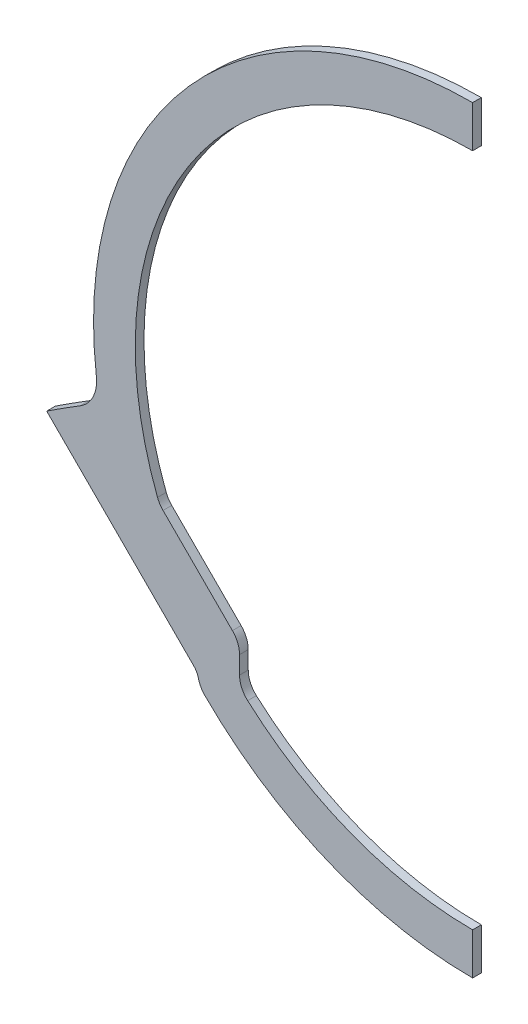
SolidWorks part; units mm, degrees
material "Balsa"
ref_plane "Front Plane" through (0, 0, 0) normal (0, 0, 1) x (1, 0, 0)
ref_plane "Top Plane" through (0, 0, 0) normal (0, 1, 0) x (1, 0, 0)
ref_plane "Right Plane" through (0, 0, 0) normal (1, 0, 0) x (0, 0, -1)
sketch "Sketch1" plane through (0, 0, 0) normal (0, 0, 1) x (1, 0, 0)
  line L0 (0, 32.094) -> (0, -346.2619) construction
  line L1 (0, 0) -> (0, 244.345) construction
  line L2 (0, 0) -> (0, 471.6969) construction
  line L3 (0, 0) -> (-283.5939, 0) construction
  line L4 (-127.2933, -32.5553) -> (-100.3525, -59.496)
  line L5 (-100.3525, -59.496) -> (-100.3525, -73.5092)
  line L6 (-100.3525, -59.496) -> (-54.3993, -105.4493) construction
  arc A0 (-54.3993, -105.4493) -> (-127.2933, -32.5553) centre (0, 21.844) ccw
  arc A2 (-100.3525, -73.5092) -> (-54.3993, -105.4493) centre (0, 21.844) ccw construction
  arc A3 (-127.2933, -32.5553) -> (-100.3525, -73.5092) centre (0, 21.844) ccw construction
  arc A4 (-100.3525, -73.5092) -> (-54.3993, -105.4493) centre (0, 21.844) ccw
  spline S2 degree 3 poles (-236.1231, -2814.3115) (289.0518, -591.4495) (268.2917, 57.6598) (49.9381, 150.9258) (45.7097, 152.4909) (37.1079, 155.2035) (32.7346, 156.3511) (27.1752, 157.5183) (26.0587, 157.7384) (23.8163, 158.1514) (22.6888, 158.3447) (19.306, 158.8811) (17.0511, 159.1813) (10.2867, 159.9126) (1.2693, 160.4377) (-7.745, 160.0789) (-14.5046, 159.4749) (-16.7575, 159.2176) (-20.1367, 158.7464) (-21.263, 158.5751) (-23.5156, 158.2037) (-24.6421, 158.0036) (-30.2426, 156.9366) (-34.6466, 155.8674) (-43.3063, 153.3113) (-47.562, 151.8242) (-55.9254, 148.4331) (-60.0331, 146.529) (-66.0807, 143.3516) (-68.0818, 142.2359) (-72.0044, 139.9197) (-73.9301, 138.7173) (-79.6017, 134.9792) (-86.884, 129.6473) (-93.6143, 123.6295) (-98.4521, 118.8554) (-100.0296, 117.2204) (-102.3424, 114.7015) (-103.1054, 113.8496) (-104.6077, 112.1297) (-105.3467, 111.2623) (-108.9818, 106.8875) (-111.6981, 103.2683) (-116.7574, 95.7975) (-119.1004, 91.9459) (-123.4121, 84.0098) (-125.3809, 79.9253) (-127.6006, 74.6695) (-128.0327, 73.61) (-128.8681, 71.4874) (-129.2719, 70.423) (-130.4422, 67.2205) (-131.1674, 65.0732) (-133.1812, 58.5951) (-135.4347, 49.861) (-136.834, 40.9354) (-137.5569, 34.168) (-137.7434, 31.9) (-137.9397, 28.4793) (-137.9911, 27.3374) (-138.0656, 25.0596) (-138.0887, 23.9223) (-138.135, 18.2442) (-137.9496, 13.7276) (-137.1441, 4.7454) (-136.5239, 0.2797) (-134.8456, -8.6005) (-133.7876, -13.015) (-131.2181, -21.791) (-129.7278, -26.0794) (-126.351, -34.4622) (-124.4643, -38.5569) (-120.2966, -46.5538) (-118.0156, -50.456) (-114.9122, -55.2108) (-114.2789, -56.1556) (-112.9868, -58.0327) (-112.3272, -58.9661) (-110.315, -61.7398) (-108.9333, -63.5482) (-104.6702, -68.8537) (-98.6716, -75.6089) (-92.0553, -81.7381) (-86.8592, -86.0978) (-85.0881, -87.5114) (-82.3719, -89.5716) (-81.4566, -90.2482) (-79.6058, -91.5811) (-78.6696, -92.238) (161.9712, -256.6405) (883.1212, 356.6582) (2158.4466, 1864.3866) knots -1.579495 -1.579495 -1.579495 -1.579495 0.03125 0.03125 0.0625 0.0625 0.09375 0.09375 0.101563 0.101563 0.109375 0.109375 0.125 0.125 0.15625 0.1875 0.1875 0.203125 0.203125 0.210937 0.210937 0.21875 0.21875 0.25 0.25 0.28125 0.28125 0.3125 0.3125 0.328125 0.328125 0.34375 0.34375 0.375 0.40625 0.40625 0.421875 0.421875 0.429687 0.429687 0.4375 0.4375 0.46875 0.46875 0.5 0.5 0.53125 0.53125 0.539062 0.539062 0.546875 0.546875 0.5625 0.5625 0.59375 0.625 0.625 0.640625 0.640625 0.648437 0.648437 0.65625 0.65625 0.6875 0.6875 0.71875 0.71875 0.75 0.75 0.78125 0.78125 0.8125 0.8125 0.84375 0.84375 0.851562 0.851562 0.859375 0.859375 0.875 0.875 0.90625 0.9375 0.9375 0.953125 0.953125 0.960937 0.960937 0.96875 0.96875 2.953647 2.953647 2.953647 2.953647 only from (66.3397, 143.1887) to (-66.0465, -100.0388)
  spline S3 degree 3 poles (66.3397, 143.1887) (62.3323, 145.3909) (58.2494, 147.3758) (49.9381, 150.9258) (45.7097, 152.4909) (37.1079, 155.2035) (32.7346, 156.3511) (27.1752, 157.5183) (26.0587, 157.7384) (23.8163, 158.1514) (22.6888, 158.3447) (19.306, 158.8811) (17.0511, 159.1813) (10.2867, 159.9126) (1.2693, 160.4377) (-7.745, 160.0789) (-14.5046, 159.4749) (-16.7575, 159.2176) (-20.1367, 158.7464) (-21.263, 158.5751) (-23.5156, 158.2037) (-24.6421, 158.0036) (-30.2426, 156.9366) (-34.6466, 155.8674) (-43.3063, 153.3113) (-47.562, 151.8242) (-55.9254, 148.4331) (-60.0331, 146.529) (-66.0807, 143.3516) (-68.0818, 142.2359) (-72.0044, 139.9197) (-73.9301, 138.7173) (-79.6017, 134.9792) (-86.884, 129.6473) (-93.6143, 123.6295) (-98.4521, 118.8554) (-100.0296, 117.2204) (-102.3424, 114.7015) (-103.1054, 113.8496) (-104.6077, 112.1297) (-105.3467, 111.2623) (-108.9818, 106.8875) (-111.6981, 103.2683) (-116.7574, 95.7975) (-119.1004, 91.9459) (-123.4121, 84.0098) (-125.3809, 79.9253) (-127.6006, 74.6695) (-128.0327, 73.61) (-128.8681, 71.4874) (-129.2719, 70.423) (-130.4422, 67.2205) (-131.1674, 65.0732) (-133.1812, 58.5951) (-135.4347, 49.861) (-136.834, 40.9354) (-137.5569, 34.168) (-137.7434, 31.9) (-137.9397, 28.4793) (-137.9911, 27.3374) (-138.0656, 25.0596) (-138.0887, 23.9223) (-138.135, 18.2442) (-137.9496, 13.7276) (-137.1441, 4.7454) (-136.5239, 0.2797) (-134.8456, -8.6005) (-133.7876, -13.015) (-131.2181, -21.791) (-129.7278, -26.0794) (-127.6847, -31.1513) (-127.3213, -32.0275) (-126.9491, -32.8995) knots 0 0 0 0 0.03125 0.03125 0.0625 0.0625 0.09375 0.09375 0.101563 0.101563 0.109375 0.109375 0.125 0.125 0.15625 0.1875 0.1875 0.203125 0.203125 0.210937 0.210937 0.21875 0.21875 0.25 0.25 0.28125 0.28125 0.3125 0.3125 0.328125 0.328125 0.34375 0.34375 0.375 0.40625 0.40625 0.421875 0.421875 0.429687 0.429687 0.4375 0.4375 0.46875 0.46875 0.5 0.5 0.53125 0.53125 0.539062 0.539062 0.546875 0.546875 0.5625 0.5625 0.59375 0.625 0.625 0.640625 0.640625 0.648437 0.648437 0.65625 0.65625 0.6875 0.6875 0.71875 0.71875 0.75 0.75 0.78125 0.78125 0.787815 0.787815 0.787815 0.787815 construction
  point P2 (0, 160.2226)
  point P3 (0, -116.9127)
  point P23 (-100.3525, -59.496)
  dimension "D1" = 277.1353
  dimension "D2" = 276.86
  dimension "D3" = 21.844
  dimension "D5" = 45
  dimension "D6" = 113.03
  dimension "D4" = 38.1
  dimension "D7" = 45
extrude "Boss-Extrude1" add sketch "Sketch1" along normal mid plane 3.175
sketch "Sketch2" plane through (0, 0, 1.5875) normal (0, 0, 1) x (1, 0, 0)
  line L2 (-114.3729, -23.9231) -> (-85.1125, -53.1834)
  line L3 (-114.3729, -23.9231) -> (-85.1125, -53.1834)
  line L4 (-85.1125, -53.1834) -> (-85.1125, -67.2157)
  line L5 (-85.1125, -53.1834) -> (-85.1125, -67.2157)
  arc A2 (-85.1125, -67.2157) -> (-114.3729, -23.9231) centre (0, 21.844) ccw
  arc A3 (-85.1125, -67.2157) -> (-114.3729, -23.9231) centre (0, 21.844) ccw
  dimension "D1" = 15.24
extrude "Cut-Extrude1" cut sketch "Sketch2" against normal up to surface (3.175 mm away) up to face at (-32.8418, -4.8687, -1.5875)
fillet "Fillet1" radius 8.89 6 edges at (-127.2933, -32.5553, 0) (-114.3729, -23.9231, 0) (-100.3525, -59.496, 0) (-100.3525, -73.5092, 0) (-85.1125, -53.1834, 0) (-85.1125, -67.2157, 0)
sketch "Sketch3" plane through (0, 0, 1.5875) normal (0, 0, 1) x (1, 0, 0)
  line L0 (-0.0002, 49.9919) -> (-0.0176, 733.2) construction
  line L1 (-0.0002, 49.9919) -> (-0.0176, 733.2) construction
  line L2 (-136.2041, -28.3557) -> (-0.0002, 49.9919) construction
  line L3 (136.2076, -28.3488) -> (-0.0002, 49.9919) construction
  line L4 (-136.2041, -28.3557) -> (-0.0002, 49.9919) construction
  line L5 (136.2076, -28.3488) -> (-0.0002, 49.9919) construction
  line L6 (-1.6539, 152.6441) -> (-1.654, 160.2641)
  line L7 (1.6481, 152.6442) -> (1.648, 160.2642)
  line L8 (-1.6539, 152.6441) -> (1.6481, 152.6442)
  line L9 (119.8485, -45.962) -> (106.7537, -38.3747)
  line L10 (121.4435, -43.2066) -> (108.3479, -35.6188)
  line L18 (121.4435, -43.2066) -> (108.3479, -35.6188)
  line L30 (-123.167, -47.8929) -> (-104.8722, -37.2914)
  line L35 (119.8485, -45.962) -> (106.7537, -38.3747)
  line L47 (108.5244, -35.721) -> (120.1169, -46.1175) construction
  line L48 (114.3206, -40.9193) -> (126.5619, -48.0121) construction
  line L49 (113.8577, -42.5592) -> (122.0137, -47.2849)
  line L50 (115.5132, -39.7021) -> (123.6691, -44.4278)
  line L51 (113.8577, -42.5592) -> (115.5132, -39.7021)
  line L52 (122.0137, -47.2849) -> (123.6691, -44.4278)
  line L58 (-124.7703, -45.1423) -> (-106.4681, -34.5364)
  line L59 (-124.7703, -45.1423) -> (-123.167, -47.8929)
  line L71 (-124.7703, -45.1423) -> (-123.167, -47.8929) construction
  line L72 (-124.7703, -45.1423) -> (-106.4681, -34.5364) construction
  line L73 (-123.167, -47.8929) -> (-104.8722, -37.2914) construction
  line L74 (-123.167, -47.8929) -> (-107.9499, -35.3951) construction
  line L75 (-115.5584, -41.644) -> (-110.9064, -38.9482) construction
  line L76 (-119.3826, -41.9518) -> (-112.6266, -38.0369)
  line L77 (-117.727, -44.8088) -> (-110.971, -40.8938)
  line L78 (-119.3826, -41.9518) -> (-117.727, -44.8088)
  line L79 (-112.6266, -38.0369) -> (-110.971, -40.8938)
  arc A0 (-54.3993, -105.4493) -> (-127.2933, -32.5553) centre (0, 21.844) ccw construction
  arc A2 (-1.654, 160.2641) -> (-130.2816, -24.9489) centre (0, 21.844) ccw construction
  arc A3 (-130.2816, -24.9489) -> (-127.2933, -32.5553) centre (0, 21.844) ccw construction
  arc A4 (-1.654, 160.2641) -> (-130.2816, -24.9489) centre (0, 21.844) ccw construction
  arc A5 (-130.2816, -24.9489) -> (-127.9919, -30.8906) centre (0, 21.844) ccw construction
  arc A14 (130.2841, -24.9419) -> (1.648, 160.2642) centre (0, 21.844) ccw construction
  arc A15 (1.648, 160.2642) -> (-1.654, 160.2641) centre (0, 21.844) ccw
  arc A16 (130.2841, -24.9419) -> (1.648, 160.2642) centre (0, 21.844) ccw construction
  arc A17 (1.648, 160.2642) -> (-1.654, 160.2641) centre (0, 21.844) ccw
  spline S0 degree 3 poles (106.7537, -38.3747) (107.2851, -37.456) (107.8165, -36.5374) (108.3479, -35.6188) knots 0 0 0 0 1 1 1 1 weights 1 1 1 1
  spline S1 degree 3 poles (119.8485, -45.962) (120.3802, -45.0435) (120.9118, -44.1251) (121.4435, -43.2066) knots 0 0 0 0 1 1 1 1 weights 1 1 1 1
  spline S2 degree 3 poles (-885.9096, -1769.7959) (-211.5315, -623.0099) (457.4335, 532.6653) (1115.294, 1687.3986) knots -628.025755 -628.025755 -628.025755 -628.025755 629.32196 629.32196 629.32196 629.32196 weights 1.00213 0.999289 0.99929 1.002132 only from (119.8485, -45.962) to (121.4435, -43.2066)
  spline S3 degree 3 poles (-1102.963, 1696.4301) (-441.8978, 540.8873) (227.2768, -614.259) (901.012, -1762.8827) knots -628.210575 -628.210575 -628.210575 -628.210575 629.142222 629.142222 629.142222 629.142222 weights 1.001328 0.999558 0.999557 1.001327 only from (-106.4681, -34.5364) to (-104.8722, -37.2914)
  spline S4 degree 3 poles (-106.4681, -34.5364) (-105.9361, -35.4547) (-105.4042, -36.373) (-104.8722, -37.2914) knots 0 0 0 0 1 1 1 1 weights 1 1 1 1 construction
  spline S6 degree 3 poles (-898.3985, -1763.0369) (-224.3104, -615.0446) (444.2624, 540.7506) (1102.1878, 1695.4772) knots -627.922228 -627.922228 -627.922228 -627.922228 629.425892 629.425892 629.425892 629.425892 weights 1.001921 0.999359 0.99936 1.001924 only from (106.7537, -38.3747) to (108.3479, -35.6188)
  point P49 (-116.0256, -43.8229)
  point P50 (120.451, -46.3794)
  arc M19 (-97.7394, -76.186) -> (-127.9919, -30.8906) centre (0, 21.844) ccw
  line M21 (-126.0584, -33.7901) -> (-102.9564, -56.8922)
  dimension "D1" = 3.302
  dimension "D2" = 7.62
  dimension "D4" = 3.302
  dimension "D5" = 7.62
  dimension "D6" = 3.302
  dimension "D7" = 5.842
extrude "Cut-Extrude2" [suppressed] cut sketch "Sketch3" against normal through all contours L79 L76 L77 M21 | L6 L8 L7 M19 | L51 L49 L50 M19
sketch "Sketch4" plane through (0, 0, 0) normal (1, 0, 0) x (0, 0, -1)
  line L1 (-96.2805, 232.7957) -> (122.2438, 232.7957)
  line L2 (-96.2805, 232.7957) -> (-96.2805, -207.8589)
  line L3 (-96.2805, -207.8589) -> (122.2438, -207.8589)
  line L4 (122.2438, 232.7957) -> (122.2438, -207.8589)
extrude "Cut-Extrude3" cut sketch "Sketch4" along normal through all
sketch "Sketch5" plane through (0, 0, 0) normal (0, 0, 1) x (1, 0, 0)
  line L0 (0, 0) -> (-220.3195, 0) construction
  line L3 (-100.3441, -70.2779) -> (-93.132, -63.0671)
  line L4 (-100.3441, -70.2779) -> (-155.5427, -15.0686)
  line L5 (-93.132, -63.0671) -> (-135.3862, -2.54)
  arc A0 (-100.3525, -69.8905) -> (-97.7394, -76.186) centre (-91.4625, -69.8905) ccw construction
  arc A1 (-135.3862, -2.54) -> (-155.5427, -15.0686) centre (85.5484, -380.4649) ccw
  dimension "D3" = 437.7663
  dimension "D1" = 120.65
  dimension "D2" = 45.006
  dimension "D4" = 135.3862
  dimension "D5" = 2.54
  dimension "D6" = 15.0686
extrude "Boss-Extrude2" add sketch "Sketch5" along normal mid plane 3.175
fillet "Fillet2" radius 12.7 1 edges at (-136.1813, -3.0059, 0)
fillet "Fillet3" radius 6.35 1 edges at (-100.3441, -70.2779, 0)
equation "\"a\"= 0.06"
equation "\"slotwidth\"=0.13"
equation "\"slotheight\"=0.3"
